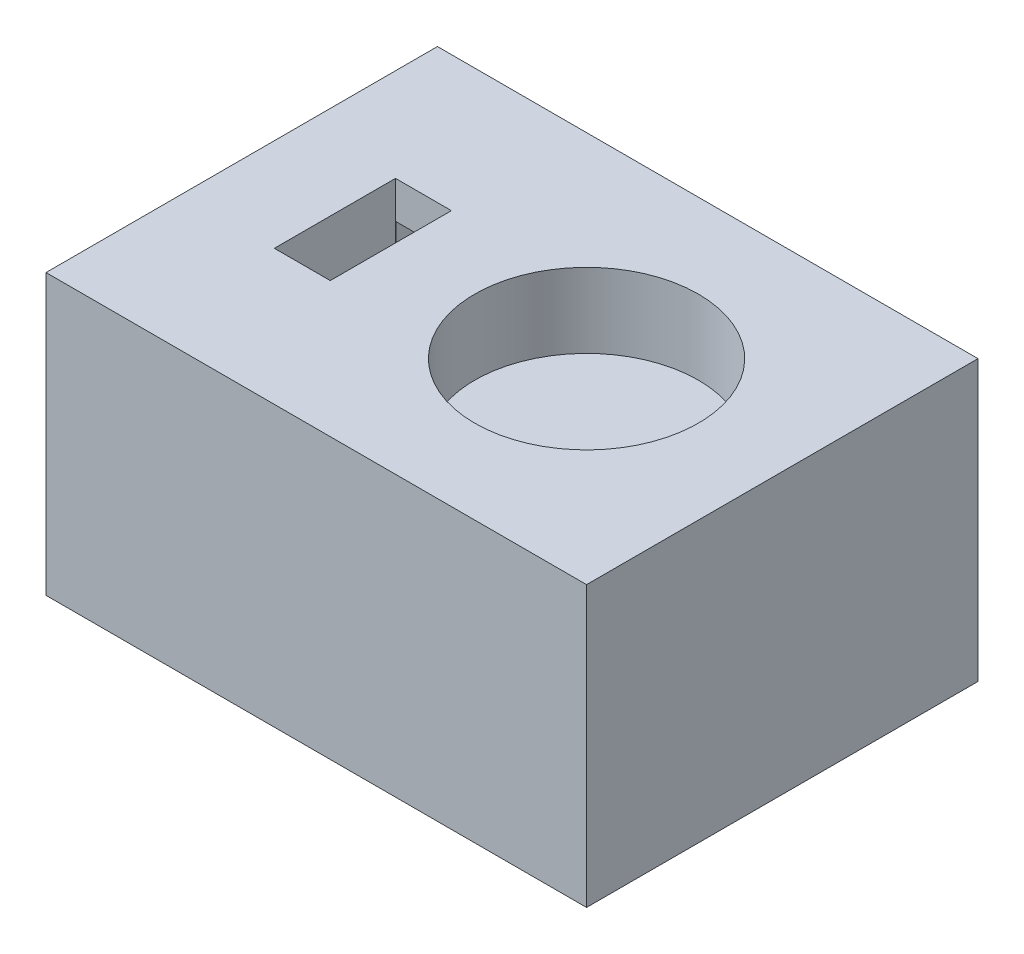
SolidWorks part; units mm, degrees
ref_plane "Plan de face" through (0, 0, 0) normal (0, 0, 1) x (1, 0, 0)
ref_plane "Plan de dessus" through (0, 0, 0) normal (0, 1, 0) x (1, 0, 0)
ref_plane "Plan de droite" through (0, 0, 0) normal (1, 0, 0) x (0, 0, -1)
sketch "Esquisse1" plane through (0, 0, 0) normal (0, 1, 0) x (1, 0, 0)
  line L1 (-21, 21) -> (21, 21)
  line L2 (-21, 21) -> (-21, -21)
  line L3 (-21, -21) -> (21, -21)
  line L4 (21, 21) -> (21, -21)
  line L5 (-21, 21) -> (21, -21) construction
  line L6 (-21, -21) -> (21, 21) construction
  point P0 (0, 0)
  dimension "D1" = 42
  dimension "D2" = 42
extrude "Boss.-Extru.1" add sketch "Esquisse1" along normal blind 30
sketch "Esquisse2" plane through (0, 30, 0) normal (0, 1, 0) x (1, 0, 0)
  circle A0 centre (0, 0) radius 12
  dimension "D1" = 24
extrude "Enlèv. mat.-Extru.1" cut sketch "Esquisse2" against normal blind 8
sketch "Esquisse3" plane through (0, 0, 21) normal (0, 0, 1) x (1, 0, 0)
  line L0 (21, 30) -> (21, 0) construction
  line L1 (-21, 30) -> (21, 30)
  line L2 (-21, 30) -> (-21, 0)
  line L3 (-21, 0) -> (21, 0)
  line L4 (21, 30) -> (21, 0)
sketch "Esquisse4" plane through (-21, 0, 0) normal (-1, 0, 0) x (0, 0, 1)
  line L0 (21, 30) -> (21, 0) construction
  line L1 (-21, 30) -> (21, 30)
  line L2 (-21, 30) -> (-21, 0)
  line L3 (-21, 0) -> (21, 0)
  line L4 (21, 30) -> (21, 0)
  line L5 (-21, 0) -> (21, 0) construction
extrude "Boss.-Extru.3" add sketch "Esquisse4" along normal blind 16
sketch "Esquisse5" plane through (0, 30, 0) normal (0, 1, 0) x (1, 0, 0)
  line L1 (-27, 6.5) -> (-21, 6.5)
  line L2 (-27, 6.5) -> (-27, -6.5)
  line L3 (-27, -6.5) -> (-21, -6.5)
  line L4 (-21, 6.5) -> (-21, -6.5)
  line L5 (21, 21) -> (-37, 21) construction
  line L7 (-37, -21) -> (-37, 21) construction
  dimension "D1" = 13
  dimension "D2" = 6
  dimension "D3" = 14.5
  dimension "D4" = 10
extrude "Enlèv. mat.-Extru.2" cut sketch "Esquisse5" against normal blind 11
sketch "Esquisse6" plane through (0, 0, -6.5) normal (0, 0, 1) x (1, 0, 0)
  line L0 (-21, 30) -> (-21, 0) construction
  line L1 (-26.9494, 20.0092) -> (-21, 20.0092)
  line L2 (-26.9494, 20.0092) -> (-26.9494, 26.0092)
  line L3 (-26.9494, 26.0092) -> (-21, 26.0092)
  line L4 (-21, 20.0092) -> (-21, 26.0092)
  dimension "D1" = 6
extrude "Enlèv. mat.-Extru.3" cut sketch "Esquisse6" against normal through all
